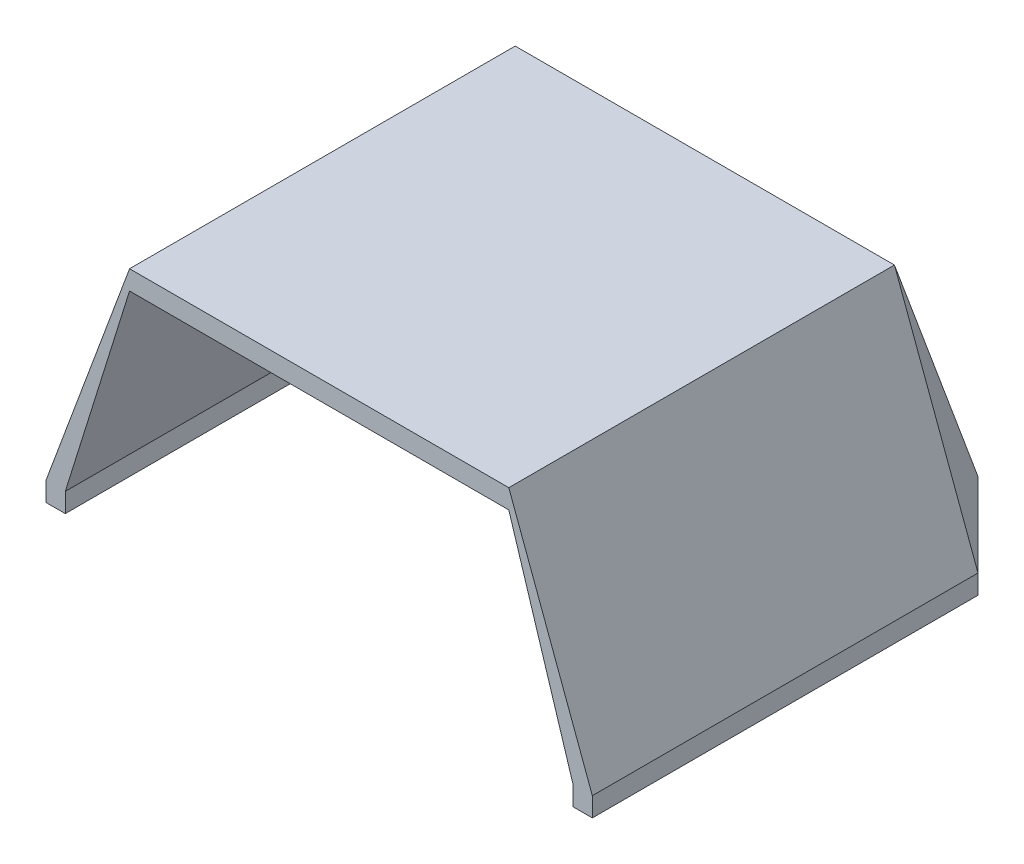
SolidWorks part; units mm, degrees
ref_plane "前视基准面" through (0, 0, 0) normal (0, 0, 1) x (1, 0, 0)
ref_plane "上视基准面" through (0, 0, 0) normal (0, 1, 0) x (1, 0, 0)
ref_plane "右视基准面" through (0, 0, 0) normal (1, 0, 0) x (0, 0, -1)
other "Configuration Table"
sketch "草图1" plane through (0, 0, 0) normal (0, 1, 0) x (1, 0, 0)
  line L0 (-13, 60) -> (-19, 60)
  line L1 (0, 0) -> (59, 0)
  line L2 (0, 0) -> (0, 60)
  line L3 (0, 60) -> (59, 60)
  line L4 (59, 0) -> (59, 60)
  line L5 (-10, 0) -> (-13, 0)
  line L6 (-10, 0) -> (-10, 60)
  line L7 (-10, 60) -> (-13, 60)
  line L8 (-13, 0) -> (-13, 60)
  line L9 (0, 70) -> (59, 70)
  line L10 (0, 70) -> (0, 73)
  line L11 (0, 73) -> (59, 73)
  line L12 (59, 70) -> (59, 73)
  line L13 (69, 60) -> (72, 60)
  line L14 (69, 60) -> (69, 0)
  line L15 (69, 0) -> (72, 0)
  line L16 (72, 60) -> (72, 0)
  line L17 (-19, 60) -> (-19, 0)
  line L18 (-19, 0) -> (-13, 0)
  line L19 (0, 73) -> (0, 79)
  line L20 (0, 79) -> (59, 79)
  line L21 (59, 79) -> (59, 73)
  line L22 (72, 60) -> (78, 60)
  line L23 (78, 60) -> (78, 0)
  line L24 (78, 0) -> (72, 0)
  circle A0 centre (-16, 15) radius 1.5
  circle A1 centre (-16, 45) radius 1.5
  circle A2 centre (75, 45) radius 1.5
  circle A3 centre (75, 15) radius 1.5
  circle A4 centre (15, 76) radius 1.5
  circle A5 centre (44, 76) radius 1.5
  point P38 (29.5, 0)
  dimension "D16" = 3
  dimension "D17" = 3
  dimension "D18" = 3
  dimension "D19" = 3
  dimension "D22" = 3
  dimension "D23" = 3
  dimension "D1" = 59
  dimension "D2" = 60
  dimension "D3" = 3
  dimension "D4" = 3
  dimension "D5" = 3
  dimension "D6" = 10
  dimension "D7" = 10
  dimension "D8" = 10
  dimension "D9" = 6
  dimension "D10" = 6
  dimension "D11" = 6
  dimension "D12" = 15
  dimension "D13" = 15
  dimension "D14" = 15
  dimension "D15" = 15
  dimension "D20" = 3
  dimension "D21" = 3
  dimension "D24" = 3
  dimension "D25" = 15
  dimension "D26" = 15
  dimension "D27" = 45.5
  dimension "D28" = 30
extrude "凸台-拉伸2" add sketch "草图1" along normal blind 3 from offset 35 contours L1 L4 L3 L2 region at (29.5, 0, -30)
extrude "凸台-拉伸3" add sketch "草图1<5>" along normal blind 3 separate body contours L8 L5 L6 L7 | L16 L13 L14 L15 | L9 L12 L11 L10 region at (-11.5, 0, -30) region at (29.5, 0, -71.5) region at (70.5, 0, -30)
sketch "草图1<5>" plane through (0, 0, 0) normal (0, 1, 0) x (1, 0, 0) same geometry as "草图1"
loft "放样1" add section face at (-11.5, 3, -30) section face at (0, 36.5, -30) connector at (-13, 3, -60) connector at (0, 38, -60)
loft "放样2" add section face at (70.5, 3, -30) section face at (59, 36.5, -30) connector at (69, 3, -60) connector at (59, 35, -60)
sketch "草图2" plane through (59, 0, 0) normal (1, 0, 0) x (0, 0, -1)
  line L0 (70, 3) -> (60, 35)
  line L1 (60, 3) -> (60, 38) construction
  line L2 (60, 35) -> (60, 38)
  line L3 (60, 38) -> (73, 3)
  line L4 (73, 3) -> (70, 3)
  line L5 (0, 0) -> (60, 0) construction
  line L6 (60, 0) -> (60, 3) construction
  line L7 (0, 3) -> (0, 0) construction
  line L8 (60, 38) -> (0, 38) construction
  line L9 (0, 38) -> (0, 3) construction
  line L10 (0, 0) -> (60, 0)
  line L11 (60, 0) -> (60, 3)
  line L12 (0, 3) -> (0, 0)
  line L13 (60, 3) -> (60, 38)
  line L14 (60, 38) -> (0, 38)
  line L15 (0, 38) -> (0, 3)
  line M7 (73, 3) -> (70, 3)
  dimension "D1" = 3
extrude "凸台-拉伸4" add sketch "草图2" against normal up to vertex (59 mm away) contours L3 L2 L0 M7 region at (59, 17.037, -66.7037) up to point (0, 38, -60)
loft "放样4" add section face at (-9.5833, 7.8333, -60) section face at (0, 13.1667, -67.4167) connector at (-10, 3, -60) connector at (0, 3, -70)
loft "放样5" add section face at (59, 13.1667, -67.4167) section face at (68.5833, 7.3333, -60) connector at (59, 3, -70) connector at (69, 3, -60)
